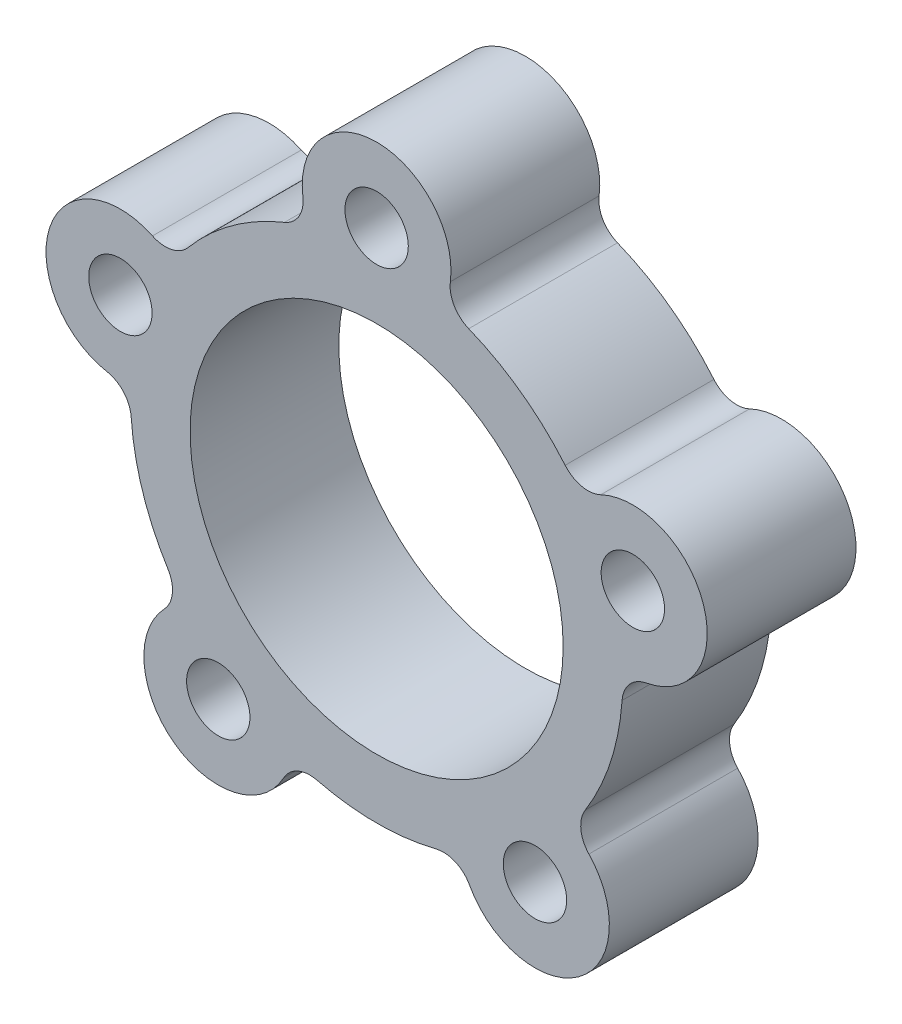
SolidWorks part; units mm, degrees
material "6061-T6 (SS)"
ref_plane "Front Plane" through (0, 0, 0) normal (0, 0, 1) x (1, 0, 0)
ref_plane "Top Plane" through (0, 0, 0) normal (0, 1, 0) x (1, 0, 0)
ref_plane "Right Plane" through (0, 0, 0) normal (1, 0, 0) x (0, 0, -1)
sketch "Sketch1" plane through (0, 0, 7.874) normal (0, 0, 1) x (1, 0, 0)
  circle A1 centre (0, 0) radius 7.9629
  circle A2 centre (0, 0) radius 7.9629
  arc A10 (8.0479, 6.7485) -> (3.9313, 9.7394) centre (0, 0) ccw
  arc A11 (3.1476, 11.0836) -> (-3.1476, 11.0836) centre (0, 11.5) ccw
  arc A12 (-3.9313, 9.7394) -> (-8.0479, 6.7485) centre (0, 0) ccw
  arc A13 (-9.5685, 6.4186) -> (-11.5138, 0.4315) centre (-10.9371, 3.5537) ccw
  arc A14 (-10.4776, -0.7292) -> (-8.9051, -5.5686) centre (0, 0) ccw
  arc A15 (-9.0612, -7.1167) -> (-3.9684, -10.817) centre (-6.7595, -9.3037) ccw
  arc A16 (-2.5442, -10.1901) -> (2.5442, -10.1901) centre (0, 0) ccw
  arc A17 (3.9684, -10.817) -> (9.0612, -7.1167) centre (6.7595, -9.3037) ccw
  arc A18 (8.9051, -5.5686) -> (10.4776, -0.7292) centre (0, 0) ccw
  arc A19 (11.5138, 0.4315) -> (9.5685, 6.4186) centre (10.9371, 3.5537) ccw
  arc A20 (8.0479, 6.7485) -> (3.9313, 9.7394) centre (0, 0) ccw
  arc A21 (3.1476, 11.0836) -> (-3.1476, 11.0836) centre (0, 11.5) ccw
  arc A22 (-3.9313, 9.7394) -> (-8.0479, 6.7485) centre (0, 0) ccw
  arc A23 (-9.5685, 6.4186) -> (-11.5138, 0.4315) centre (-10.9371, 3.5537) ccw
  arc A24 (-10.4776, -0.7292) -> (-8.9051, -5.5686) centre (0, 0) ccw
  arc A25 (-9.0612, -7.1167) -> (-3.9684, -10.817) centre (-6.7595, -9.3037) ccw
  arc A26 (-2.5442, -10.1901) -> (2.5442, -10.1901) centre (0, 0) ccw
  arc A27 (3.9684, -10.817) -> (9.0612, -7.1167) centre (6.7595, -9.3037) ccw
  arc A28 (8.9051, -5.5686) -> (10.4776, -0.7292) centre (0, 0) ccw
  arc A29 (11.5138, 0.4315) -> (9.5685, 6.4186) centre (10.9371, 3.5537) ccw
  arc A72 (8.0479, 6.7485) -> (9.5685, 6.4186) centre (9.0211, 7.5645) ccw
  arc A73 (8.0479, 6.7485) -> (9.5685, 6.4186) centre (9.0211, 7.5645) ccw
  arc A74 (3.1476, 11.0836) -> (3.9313, 9.7394) centre (4.4066, 10.9171) ccw
  arc A75 (3.1476, 11.0836) -> (3.9313, 9.7394) centre (4.4066, 10.9171) ccw
  arc A76 (-3.9313, 9.7394) -> (-3.1476, 11.0836) centre (-4.4066, 10.9171) ccw
  arc A77 (-3.9313, 9.7394) -> (-3.1476, 11.0836) centre (-4.4066, 10.9171) ccw
  arc A78 (-9.5685, 6.4186) -> (-8.0479, 6.7485) centre (-9.0211, 7.5645) ccw
  arc A79 (-9.5685, 6.4186) -> (-8.0479, 6.7485) centre (-9.0211, 7.5645) ccw
  arc A80 (-10.4776, -0.7292) -> (-11.5138, 0.4315) centre (-11.7445, -0.8174) ccw
  arc A81 (-10.4776, -0.7292) -> (-11.5138, 0.4315) centre (-11.7445, -0.8174) ccw
  arc A82 (-9.0612, -7.1167) -> (-8.9051, -5.5686) centre (-9.9819, -6.242) ccw
  arc A83 (-9.0612, -7.1167) -> (-8.9051, -5.5686) centre (-9.9819, -6.242) ccw
  arc A84 (-2.5442, -10.1901) -> (-3.9684, -10.817) centre (-2.8519, -11.4223) ccw
  arc A85 (-2.5442, -10.1901) -> (-3.9684, -10.817) centre (-2.8519, -11.4223) ccw
  arc A86 (3.9684, -10.817) -> (2.5442, -10.1901) centre (2.8519, -11.4223) ccw
  arc A87 (3.9684, -10.817) -> (2.5442, -10.1901) centre (2.8519, -11.4223) ccw
  arc A88 (8.9051, -5.5686) -> (9.0612, -7.1167) centre (9.9819, -6.242) ccw
  arc A89 (8.9051, -5.5686) -> (9.0612, -7.1167) centre (9.9819, -6.242) ccw
  arc A90 (11.5138, 0.4315) -> (10.4776, -0.7292) centre (11.7445, -0.8174) ccw
  arc A91 (11.5138, 0.4315) -> (10.4776, -0.7292) centre (11.7445, -0.8174) ccw
  dimension "D1" = 0
  dimension "D2" = 0
extrude "Boss-Extrude1" add sketch "Sketch1" along normal blind 6.35
sketch "Sketch4" plane through (0, 0, 14.224) normal (0, 0, 1) x (1, 0, 0)
  point P0 (-10.9371, 3.5537)
  point P3 (0, 11.5)
  point P6 (10.9371, 3.5537)
  point P9 (6.7595, -9.3037)
  point P12 (-6.7595, -9.3037)
hole_wizard "#6-32 Tapped Hole1" positions "Sketch4" profile "Sketch3" tap size "#6-32" standard "ANSI Inch" end condition through all
sketch "Sketch3" plane through (-10.9371, 3.5537, 14.224) normal (1, 0, 0) x (0, -1, 0)
  line L0 (0, 0) -> (0, 6.35)
  line L1 (0, 6.35) -> (1.3525, 6.35)
  line L2 (1.3525, 6.35) -> (1.3525, 0)
  line L5 (1.3525, 0) -> (0, 0)
  line L11 (0, -6.35) -> (0, 107.95) construction
  dimension "Thru Tap Drill Dia." = 2.7051
  dimension "Thru Tap Drill Depth" = 6.35
cosmetic thread "Hole Thread1" parameters "D2"=3.5052
cosmetic thread "Hole Thread2" parameters "D2"=3.5052
cosmetic thread "Hole Thread3" parameters "D2"=3.5052
cosmetic thread "Hole Thread4" parameters "D2"=3.5052
cosmetic thread "Hole Thread5" parameters "D2"=3.5052
